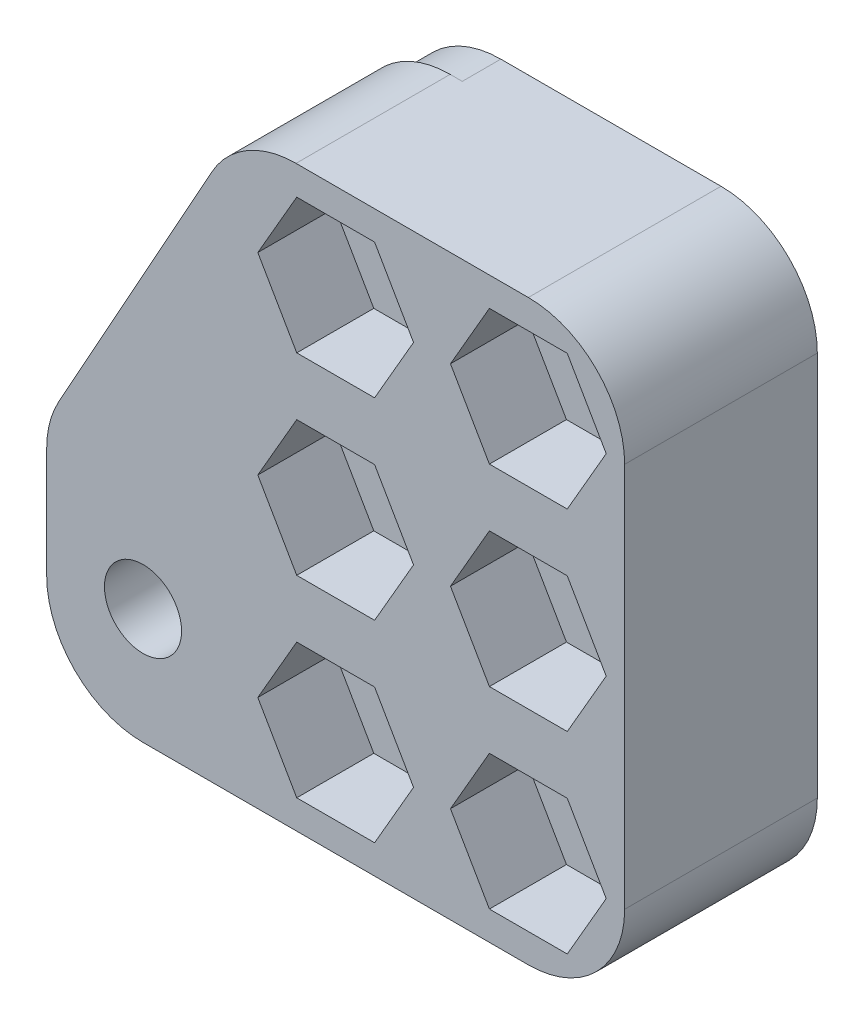
SolidWorks part; units mm, degrees
ref_plane "Front Plane" through (0, 0, 0) normal (0, 0, 1) x (1, 0, 0)
ref_plane "Top Plane" through (0, 0, 0) normal (0, 1, 0) x (1, 0, 0)
ref_plane "Right Plane" through (0, 0, 0) normal (1, 0, 0) x (0, 0, -1)
sketch "Sketch1" plane through (0, 0, 0) normal (0, 0, 1) x (1, 0, 0)
  line L0 (-6.35, 31.75) -> (-19.05, 8.89)
  line L1 (-6.35, -6.35) -> (19.05, -6.35)
  line L3 (-6.35, 31.75) -> (19.05, 31.75)
  line L4 (19.05, -6.35) -> (19.05, 31.75)
  line L5 (-19.05, 8.89) -> (-19.05, -6.35)
  line L6 (-19.05, -6.35) -> (-6.35, -6.35)
  circle A0 centre (0, 0) radius 2.286
  circle A1 centre (-12.7, 1.27) radius 2.54
  circle A2 centre (12.7, 0) radius 2.286
  circle A3 centre (12.7, 12.7) radius 2.286
  circle A4 centre (12.7, 25.4) radius 2.286
  circle A5 centre (0, 12.7) radius 2.286
  circle A6 centre (0, 25.4) radius 2.286
  dimension "D7" = 4.572
  dimension "D8" = 5.08
  dimension "D1" = 7.62
  dimension "D2" = 6.35
  dimension "D3" = 12.7
  dimension "D4" = 25.4
  dimension "D5" = 15.24
  dimension "D6" = 6.35
  dimension "D11" = 6.35
  dimension "1.5" = 38.1
  dimension "D9" = 2
  dimension "D10" = 3
extrude "Boss-Extrude1" add sketch "Sketch1" along normal blind 12.7
fillet "Fillet1" radius 6.35 5 edges at (-19.05, 8.89, 6.35) (-6.35, 31.75, 6.35) (19.05, 31.75, 6.35) (19.05, -6.35, 6.35) (-19.05, -6.35, 6.35)
sketch "Sketch2" plane through (0, 0, 12.7) normal (0, 0, 1) x (1, 0, 0)
  line L0 (17.8326, 0) -> (15.2663, 4.445)
  line L1 (5.1326, 0) -> (2.5663, 4.445)
  line L2 (2.5663, 4.445) -> (-2.5663, 4.445)
  line L3 (-2.5663, 4.445) -> (-5.1326, 0)
  line L4 (-5.1326, 0) -> (-2.5663, -4.445)
  line L5 (-2.5663, -4.445) -> (2.5663, -4.445)
  line L6 (2.5663, -4.445) -> (5.1326, 0)
  line L7 (15.2663, 4.445) -> (10.1337, 4.445)
  line L8 (10.1337, 4.445) -> (7.5674, 0)
  line L9 (7.5674, 0) -> (10.1337, -4.445)
  line L10 (10.1337, -4.445) -> (15.2663, -4.445)
  line L11 (15.2663, -4.445) -> (17.8326, 0)
  line L12 (17.8326, 12.7) -> (15.2663, 17.145)
  line L13 (15.2663, 17.145) -> (10.1337, 17.145)
  line L14 (10.1337, 17.145) -> (7.5674, 12.7)
  line L15 (7.5674, 12.7) -> (10.1337, 8.255)
  line L16 (10.1337, 8.255) -> (15.2663, 8.255)
  line L17 (15.2663, 8.255) -> (17.8326, 12.7)
  line L18 (17.8326, 25.4) -> (15.2663, 29.845)
  line L19 (15.2663, 29.845) -> (10.1337, 29.845)
  line L20 (10.1337, 29.845) -> (7.5674, 25.4)
  line L21 (7.5674, 25.4) -> (10.1337, 20.955)
  line L22 (10.1337, 20.955) -> (15.2663, 20.955)
  line L23 (15.2663, 20.955) -> (17.8326, 25.4)
  line L24 (5.1326, 12.7) -> (2.5663, 17.145)
  line L25 (2.5663, 17.145) -> (-2.5663, 17.145)
  line L26 (-2.5663, 17.145) -> (-5.1326, 12.7)
  line L27 (-5.1326, 12.7) -> (-2.5663, 8.255)
  line L28 (-2.5663, 8.255) -> (2.5663, 8.255)
  line L29 (2.5663, 8.255) -> (5.1326, 12.7)
  line L30 (5.1326, 25.4) -> (2.5663, 29.845)
  line L31 (2.5663, 29.845) -> (-2.5663, 29.845)
  line L32 (-2.5663, 29.845) -> (-5.1326, 25.4)
  line L33 (-5.1326, 25.4) -> (-2.5663, 20.955)
  line L34 (-2.5663, 20.955) -> (2.5663, 20.955)
  line L35 (2.5663, 20.955) -> (5.1326, 25.4)
  circle A0 centre (0, 0) radius 4.445 construction
  circle A1 centre (12.7, 0) radius 4.445 construction
  circle A2 centre (12.7, 12.7) radius 4.445 construction
  circle A3 centre (12.7, 25.4) radius 4.445 construction
  circle A4 centre (0, 12.7) radius 4.445 construction
  circle A5 centre (0, 25.4) radius 4.445 construction
  dimension "D1" = 8.89
  dimension "D2" = 2
  dimension "D3" = 3
extrude "Cut-Extrude1" cut sketch "Sketch2" against normal blind 5.08
sketch "Sketch3" plane through (0, 0, 0) normal (0, 0, -1) x (-1, 0, 0)
  line L5 (8.1645, 28.4838) -> (8.1645, -6.35)
  line L10 (19.05, 0) -> (19.05, 7.2445)
  line L11 (-12.7, -6.35) -> (12.7, -6.35)
  line L12 (-19.05, 25.4) -> (-19.05, 0)
  line L13 (2.6136, 31.75) -> (-12.7, 31.75)
  line L14 (18.2509, 10.3284) -> (8.1645, 28.4838)
  line L15 (19.05, 0) -> (19.05, 7.2445)
  line L16 (-12.7, -6.35) -> (12.7, -6.35)
  line L17 (-19.05, 25.4) -> (-19.05, 0)
  line L18 (2.6136, 31.75) -> (-12.7, 31.75)
  line L19 (18.2509, 10.3284) -> (8.1645, 28.4838)
  arc A10 (19.05, 7.2445) -> (18.2509, 10.3284) centre (12.7, 7.2445) ccw
  arc A11 (12.7, -6.35) -> (19.05, 0) centre (12.7, 0) ccw
  arc A12 (-19.05, 0) -> (-12.7, -6.35) centre (-12.7, 0) ccw
  arc A13 (-12.7, 31.75) -> (-19.05, 25.4) centre (-12.7, 25.4) ccw
  arc A14 (8.1645, 28.4838) -> (2.6136, 31.75) centre (2.6136, 25.4) ccw
  arc A15 (19.05, 7.2445) -> (18.2509, 10.3284) centre (12.7, 7.2445) ccw
  arc A16 (12.7, -6.35) -> (19.05, 0) centre (12.7, 0) ccw
  arc A17 (-19.05, 0) -> (-12.7, -6.35) centre (-12.7, 0) ccw
  arc A18 (-12.7, 31.75) -> (-19.05, 25.4) centre (-12.7, 25.4) ccw
  arc A19 (8.1645, 28.4838) -> (2.6136, 31.75) centre (2.6136, 25.4) ccw
  line M11 (19.05, 0) -> (19.05, 7.2445)
  arc M12 (19.05, 7.2445) -> (18.2509, 10.3284) centre (12.7, 7.2445) ccw
  line M13 (18.2509, 10.3284) -> (8.1645, 28.4838)
  line M19 (-12.7, -6.35) -> (12.7, -6.35)
  arc M20 (12.7, -6.35) -> (19.05, 0) centre (12.7, 0) ccw
  circle M22 centre (12.7, 1.27) radius 2.54
  dimension "D1" = 0
extrude "Cut-Extrude2" cut sketch "Sketch3" against normal blind 2.54 contours L5 M13 M19 M20 M11 M12 M22 region at (-12.7399, 7.684, 0)
fillet "Fillet2" radius 6.35 2 edges at (-8.1645, -6.35, 1.27) (-8.1645, 28.4838, 1.27)
